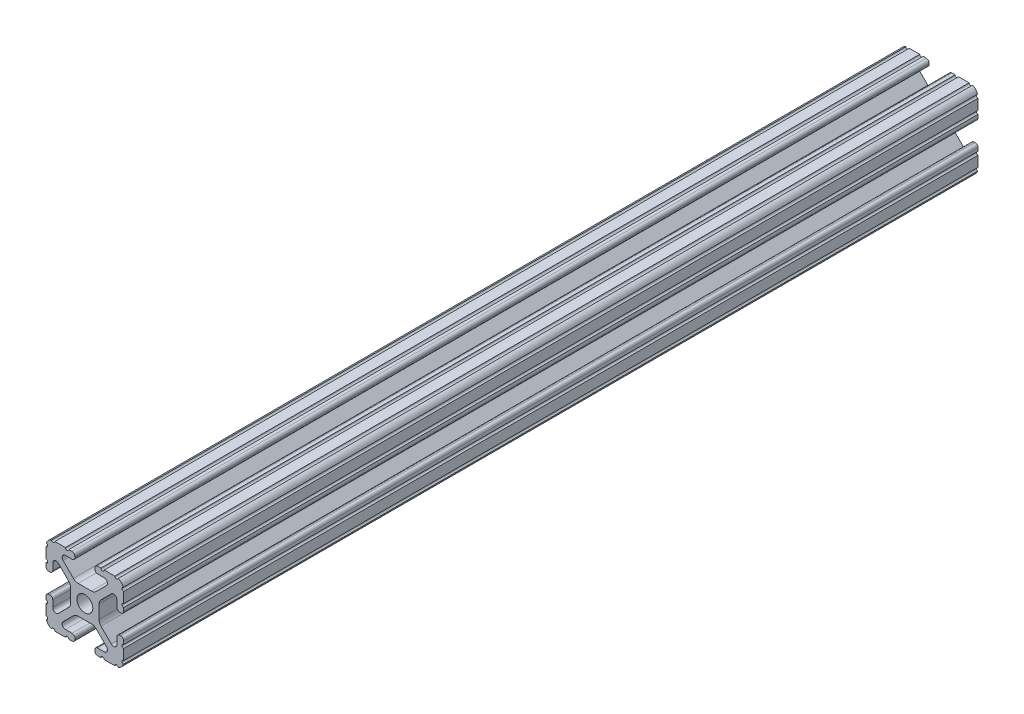
SolidWorks part; units mm, degrees
ref_plane "Front Plane" through (0, 0, 0) normal (0, 0, 1) x (1, 0, 0)
ref_plane "Top Plane" through (0, 0, 0) normal (0, 1, 0) x (1, 0, 0)
ref_plane "Right Plane" through (0, 0, 0) normal (1, 0, 0) x (0, 0, -1)
sketch "Sketch2" plane through (0, 0, 0) normal (0, 0, 1) x (1, 0, 0)
  line L0 (0, 12.7) -> (0, -12.7) construction
  line L1 (-12.7, 0) -> (12.7, 0) construction
  line L2 (3.2512, -12.7) -> (12.7, -12.7)
  line L3 (12.7, -12.7) -> (12.7, -3.2512)
  line L4 (3.2512, -12.7) -> (3.2512, -10.4902)
  line L5 (3.2512, -10.4902) -> (8.9276, -10.4902)
  line L6 (8.9276, -10.4902) -> (3.0856, -4.6482)
  line L7 (0, 0) -> (12.7, -12.7) construction
  line L8 (12.7, -3.2512) -> (10.4902, -3.2512)
  line L9 (10.4902, -3.2512) -> (10.4902, -8.9276)
  line L10 (10.4902, -8.9276) -> (4.6482, -3.0856)
  circle A0 centre (0, 0) radius 2.6035
  arc A1 (6.3485, -10.4902) -> (7.1039, -8.6665) centre (6.3485, -9.4219) ccw construction
  point P8 (0, -4.6482)
  dimension "Center Hole Diameter" = 5.207
  dimension "Rail Height" = 25.4
  dimension "Rail Width" = 25.4
  dimension "T-Slot Width" = 6.5024
  dimension "Slot Inner Width" = 14.8336
  dimension "Thickness" = 2.2098
  dimension "Slot Depth" = 5.842
  dimension "D1" = 2.2098
sketch "Sketch3" plane through (0, 0, 0) normal (1, 0, 0) x (0, 0, -1)
  line L0 (-139.7361, -12.7) -> (139.7361, -12.7) construction
  line L1 (-114.3361, 0) -> (114.3361, 0) construction
  line L2 (139.7361, 0) -> (-139.7361, 0) construction
sketch "Sketch4" plane through (0, 0, 0) normal (0, 0, 1) x (1, 0, 0)
  line L0 (4.1904, -12.7) -> (10.1173, -12.7)
  line L1 (3.2512, -12.7) -> (12.7, -12.7) construction
  line L2 (3.2512, -12.7) -> (3.2512, -10.4902) construction
  line L3 (3.2512, -10.4902) -> (8.9276, -10.4902) construction
  line L4 (3.2512, -11.4294) -> (3.2512, -11.7608)
  line L5 (4.1904, -10.4902) -> (6.3485, -10.4902)
  line L6 (0, -4.6482) -> (2.164, -4.6482)
  line L7 (8.9276, -10.4902) -> (3.0856, -4.6482) construction
  line L8 (3.7373, -5.2999) -> (7.1039, -8.6665)
  line L9 (12.7, -12.7) -> (12.7, -3.2512) construction
  line L10 (10.4902, -8.9276) -> (4.6482, -3.0856) construction
  line L11 (10.4902, -3.2512) -> (10.4902, -8.9276) construction
  line L12 (10.4902, -6.3485) -> (10.4902, -4.1904)
  line L13 (12.7, -3.2512) -> (10.4902, -3.2512) construction
  line L14 (11.4294, -3.2512) -> (11.7608, -3.2512)
  line L15 (12.7, -4.1904) -> (12.7, -10.1173)
  line L16 (8.6665, -7.1039) -> (5.2999, -3.7373)
  line L17 (4.6482, 0) -> (4.6482, -2.164)
  line L18 (-12.7, 0) -> (12.7, 0) construction
  line L19 (0, -4.6482) -> (0, -2.6035)
  line L20 (0, 12.7) -> (0, -12.7) construction
  line L21 (4.6482, 0) -> (2.6035, 0)
  arc A0 (3.2512, -11.7608) -> (4.1904, -12.7) centre (4.1904, -11.7608) ccw
  arc A2 (3.2512, -11.4294) -> (4.1904, -10.4902) centre (4.1904, -11.4294) cw
  arc A3 (6.3485, -10.4902) -> (7.1039, -8.6665) centre (6.3485, -9.4219) ccw
  arc A4 (2.164, -4.6482) -> (3.7373, -5.2999) centre (2.164, -6.8732) cw
  arc A5 (10.1173, -12.7) -> (12.7, -10.1173) centre (10.1173, -10.1173) ccw
  arc A6 (8.6665, -7.1039) -> (10.4902, -6.3485) centre (9.4219, -6.3485) ccw
  arc A7 (10.4902, -4.1904) -> (11.4294, -3.2512) centre (11.4294, -4.1904) cw
  arc A8 (11.7608, -3.2512) -> (12.7, -4.1904) centre (11.7608, -4.1904) cw
  arc A9 (5.2999, -3.7373) -> (4.6482, -2.164) centre (6.8732, -2.164) cw
  circle A10 centre (0, 0) radius 2.6035 construction
  arc A11 (0, -2.6035) -> (2.6035, 0) centre (0, 0) ccw
  dimension "D1" = 2.5827
  dimension "D2" = 2.225
  dimension "D3" = 0.9392
extrude "Boss-Extrude1" add sketch "Sketch4" along normal up to vertex (139.7361 mm away) from vertex up to point (0, -12.7, 139.7361) starting at point (0, -12.7, -139.7361)
sketch "Sketch5" plane through (0, 0, 0) normal (0, 0, 1) x (1, 0, 0)
  line L0 (3.2512, -12.7) -> (12.7, -12.7) construction
  line L1 (4.1904, -10.4902) -> (6.3485, -10.4902) construction
  line L3 (0, 0) -> (12.7, -12.7) construction
  line L4 (6.3485, -10.4902) -> (6.3485, -12.7) construction
  line L5 (8.9276, -10.4902) -> (3.0856, -4.6482) construction
  circle A0 centre (10.3562, -12.7) radius 0.5524
  circle A1 centre (5.796, -12.7) radius 0.5524
  circle A2 centre (12.7, -10.3562) radius 0.5524
  circle A3 centre (12.7, -5.796) radius 0.5524
  point P10 (5.2694, -10.4902)
  point P12 (9.4219, -6.3485)
  dimension "D1" = 1.1049
extrude "Cut-Extrude1" cut sketch "Sketch5" against normal through all both and the other way through all
mirror "Mirror1" about plane through (0, 0, 0) normal (1, 0, 0) of bodies 137 134
mirror "Mirror2" about plane through (0, 0, 0) normal (0, 1, 0) of bodies 135
equation "\"D1@Sketch2\"=\"Thickness@Sketch2\""
equation "\"D2@Sketch4\"=\"Slot Inner Width@Sketch2\"*0.15"
equation "\"D1@Sketch4\"=\"D3@Sketch4\"*2.75"
equation "\"D3@Sketch4\"=\"Thickness@Sketch2\"*0.425"
equation "\"D1@Sketch5\"=\"Thickness@Sketch2\"*0.5"
equation "\"D1@Boss-Extrude1\"=\"Length@Sketch3\""
